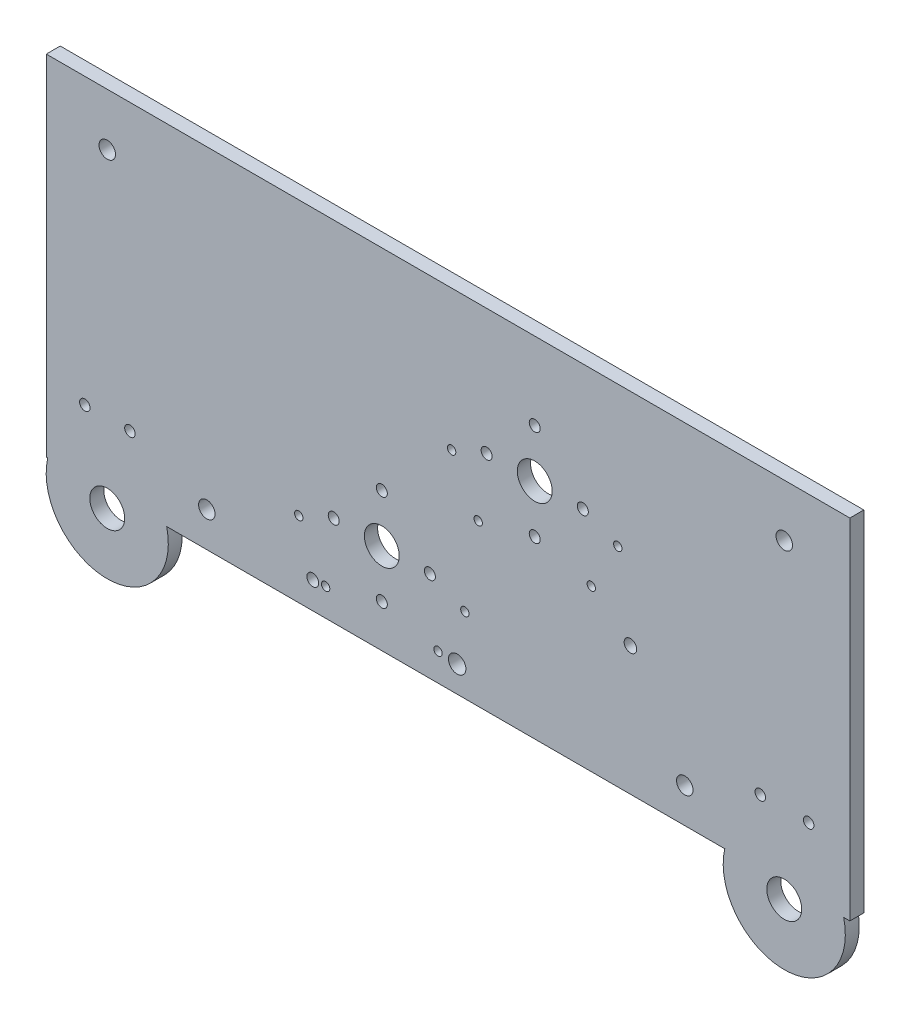
SolidWorks part; units mm, degrees
ref_plane "Front Plane" through (0, 0, 0) normal (0, 0, 1) x (1, 0, 0)
ref_plane "Top Plane" through (0, 0, 0) normal (0, 1, 0) x (1, 0, 0)
ref_plane "Right Plane" through (0, 0, 0) normal (1, 0, 0) x (0, 0, -1)
sketch "Sketch2" plane through (0, 0, 0) normal (0, 0, 1) x (1, 0, 0)
  line L1 (-143.383, -31.75) -> (143.383, -31.75)
  line L2 (-143.383, -31.75) -> (-143.383, 31.75)
  line L3 (-143.383, 31.75) -> (143.383, 31.75)
  line L4 (143.383, -31.75) -> (143.383, 31.75)
  line L5 (-143.383, -31.75) -> (143.383, 31.75) construction
  line L6 (-143.383, 31.75) -> (143.383, -31.75) construction
  line L16 (-143.383, 31.75) -> (143.383, 31.75)
  line L17 (-143.383, 31.75) -> (-143.383, 95.25)
  line L18 (-143.383, 95.25) -> (143.383, 95.25)
  line L19 (143.383, 31.75) -> (143.383, 95.25)
  circle A0 centre (-123.317, -36.83) radius 6.35
  circle A1 centre (123.063, -36.83) radius 6.35
  point P0 (0, 0)
  dimension "D3" = 20.066
  dimension "D5" = 5.08
  dimension "D7" = 63.5
  dimension "D1" = 63.5
  dimension "D2" = 286.766
  dimension "D6" = 20.32
extrude "Boss-Extrude1" add sketch "Sketch2" against normal blind 5.0749 contours A1 L1 L4 L3 L2 A0 | L3 L19 L18 L17 region at (0.0001, 0.0226, 0) region at (0, 63.5, 0)
ref_plane "Plane1" through (-143.383, 95.25, 0) normal (0, 1, 0) x (1, 0, 0)
ref_plane "Plane2" through (0, 0, -5.0749) normal (0, 0, -1) x (-1, 0, 0)
sketch "Sketch6" plane through (0, 0, -5.0749) normal (0, 0, -1) x (-1, 0, 0)
  line L0 (-116.713, -36.83) -> (-129.413, -36.83) construction
  line L1 (-123.063, -30.48) -> (-123.063, -43.18) construction
  line L3 (123.317, -30.48) -> (123.317, -43.18) construction
  line L4 (123.317, -43.18) -> (116.967, -36.83) construction
  line L6 (116.967, -36.83) -> (129.667, -36.83) construction
  circle A2 centre (-123.063, -36.83) radius 6.35 construction
  circle A3 centre (-123.063, -36.83) radius 22.225
  circle A4 centre (123.317, -36.83) radius 6.35 construction
  circle A5 centre (123.317, -36.83) radius 22.225
  dimension "D1" = 44.45
  dimension "D2" = 44.45
extrude "Boss-Extrude3" add sketch "Sketch6" against normal blind 5.0749
extrude "Cut-Extrude2" cut sketch "Sketch2<3>" against normal blind 5.588 contours A0 | A1
sketch "Sketch2<3>" plane through (0, 0, 0) normal (0, 0, 1) x (1, 0, 0) same geometry as "Sketch2"
sketch "Sketch8" plane through (0, 0, -5.0749) normal (0, 0, -1) x (-1, 0, 0)
  line L0 (145.5039, -31.75) -> (145.5039, 95.25) construction
  line L1 (198.383, 95.25) -> (88.383, 95.25) construction
  line L2 (143.383, -27.2746) -> (143.383, 95.25) construction
  line L3 (101.6804, -31.75) -> (170.7618, -31.75) construction
  line L4 (145.5039, 95.25) -> (142.7757, 95.25)
  line L5 (145.5039, 95.25) -> (145.5039, -31.75)
  line L6 (145.5039, -31.75) -> (142.7757, -31.75)
  line L7 (142.7757, 95.25) -> (142.7757, -31.75)
  dimension "D1" = 2.1209
extrude "Boss-Extrude4" add sketch "Sketch8" against normal blind 5.0749
sketch "Sketch9" plane through (0, 0, -5.0749) normal (0, 0, -1) x (-1, 0, 0)
  line L0 (-114.4501, -31.75) -> (-154.5549, -31.75) construction
  line L1 (-146.9463, 95.25) -> (-143.383, 95.25)
  line L2 (-146.9463, 95.25) -> (-146.9463, -31.75)
  line L3 (-146.9463, -31.75) -> (-143.383, -31.75)
  line L4 (-143.383, 95.25) -> (-143.383, -31.75)
  line L5 (-143.383, -27.8273) -> (-143.383, 95.25) construction
  line L6 (101.6804, -31.75) -> (-101.4264, -31.75) construction
  dimension "D1" = 3.5633
extrude "Boss-Extrude5" add sketch "Sketch9" against normal blind 5.0749
sketch "Sketch12" plane through (0, 0, 0) normal (0, 0, 1) x (1, 0, 0)
  line L0 (-123.317, -43.18) -> (-123.317, 95.25) construction
  line L1 (-145.5039, 95.25) -> (146.9463, 95.25) construction
  line L2 (-123.317, 95.25) -> (123.063, -43.18) construction
  line L3 (123.063, -43.18) -> (123.063, 95.25) construction
  line L4 (123.063, 95.25) -> (-123.317, -43.18) construction
  line L5 (-123.317, -43.18) -> (-123.317, 76.2) construction
  line L6 (-123.317, 76.2) -> (123.063, 76.2) construction
  circle A0 centre (-123.317, -36.83) radius 6.35 construction
  circle A1 centre (123.063, -36.83) radius 6.35 construction
  circle A2 centre (-123.317, 76.2) radius 3
  circle A3 centre (123.063, 76.2) radius 3
  dimension "D1" = 19.05
extrude "Cut-Extrude3" cut sketch "Sketch12" against normal blind 400.05
sketch "Sketch13" plane through (0, 0, -5.0749) normal (0, 0, -1) x (-1, 0, 0)
  line L0 (101.6804, -31.75) -> (-101.4264, -31.75) construction
  line L3 (-146.9463, 95.25) -> (-146.9463, -31.75) construction
  circle A0 centre (23.3906, 1.27) radius 22.86
  circle A1 centre (-32.258, 49.53) radius 22.86
  circle A4 centre (-32.258, 67.0306) radius 2
  circle A5 centre (-14.7574, 49.53) radius 2
  circle A6 centre (-32.258, 32.0294) radius 2
  circle A7 centre (-49.7586, 49.53) radius 2
  circle A8 centre (23.3906, 18.7706) radius 2
  circle A9 centre (40.8912, 1.27) radius 2
  circle A10 centre (23.3906, -16.2306) radius 2
  circle A11 centre (5.89, 1.27) radius 2
  circle A12 centre (-32.258, 49.53) radius 6.35
  circle A13 centre (23.3906, 1.27) radius 6.35
  dimension "D1" = 33.02
  dimension "D3" = 81.28
  dimension "D4" = 45.72
  dimension "D6" = 17.5006
  dimension "D2" = 114.6883
  dimension "D5" = 73.66
  dimension "D7" = 17.5006
  dimension "D8" = 17.5006
  dimension "D9" = 17.5006
  dimension "D10" = 17.5006
  dimension "D11" = 17.5006
  dimension "D12" = 17.5006
  dimension "D13" = 17.5006
ref_plane "Plane3" through (0, 0, -114.2949) normal (0, 0, -1) x (-1, 0, 0)
mirror "Mirror1" about plane through (0, 0, -114.2949) normal (0, 0, -1) of bodies 108 110
delete or keep bodies "Body-Delete/Keep 1" type delete bodies bodies 108
extrude "Cut-Extrude10" cut sketch "Sketch13<3>" along normal blind 1549.4 contours A8 | A11 | A9 | A10 | A4 | A5 | A6 | A7 region at (32.258, 67.0306, -5.0749) region at (14.7574, 49.53, -5.0749) region at (32.258, 32.0294, -5.0749) region at (49.7586, 49.53, -5.0749) region at (-23.3906, 18.7706, -5.0749) region at (-40.8912, 1.27, -5.0749) region at (-23.3906, -16.2306, -5.0749) region at (-5.89, 1.27, -5.0749)
sketch "Sketch13<3>" plane through (0, 0, -5.0749) normal (0, 0, -1) x (-1, 0, 0) same geometry as "Sketch13"
sketch "Sketch15" plane through (0, 0, -223.5149) normal (0, 0, 1) x (1, 0, 0)
  line L0 (-145.5039, -31.75) -> (-145.5039, 95.25) construction
  line L2 (-101.6804, -31.75) -> (101.4264, -31.75) construction
  line L3 (146.9463, 95.25) -> (146.9463, -31.75) construction
  circle A0 centre (-87.0839, -19.05) radius 2.9972
  circle A1 centre (86.868, -19.05) radius 2.9972
  dimension "D1" = 58.42
  dimension "D2" = 60.0783
  dimension "D3" = 12.7
  dimension "D4" = 12.7
extrude "Cut-Extrude11" cut sketch "Sketch15" against normal blind 1549.4
extrude "Cut-Extrude12" cut sketch "Sketch13<4>" along normal blind 1549.4 contours A13 | A12 region at (32.258, 49.53, -5.0749) region at (-23.3906, 1.27, -5.0749)
sketch "Sketch13<4>" plane through (0, 0, -5.0749) normal (0, 0, -1) x (-1, 0, 0) same geometry as "Sketch13"
extrude "Cut-Extrude13" cut sketch "Sketch13" along normal blind 1549.4 from offset 223.266
sketch "Sketch16" plane through (0, 0, -223.5149) normal (0, 0, 1) x (1, 0, 0)
  line L0 (32.258, 18.8185) -> (32.258, 26.7289) construction
  line L1 (32.258, 26.7289) -> (11.6837, 26.7289) construction
  line L2 (11.6837, 26.7289) -> (52.8323, 26.7289) construction
  line L3 (52.8323, 26.7289) -> (62.4869, 44.1073) construction
  line L4 (62.4869, 44.1073) -> (2.0074, 44.2293) construction
  line L5 (-23.3906, -29.464) -> (-23.3906, -21.6773) construction
  line L6 (-23.3906, -21.6773) -> (-2.9456, -21.6773) construction
  line L7 (-2.9456, -21.6773) -> (-43.8357, -21.6773) construction
  line L8 (-43.8357, -21.6773) -> (-53.6181, -4.2867) construction
  line L9 (-53.6181, -4.2867) -> (6.8369, -4.2867) construction
  line L10 (6.8369, -4.2867) -> (-2.9456, -21.6773) construction
  circle A0 centre (-23.3906, 1.27) radius 30.734
  circle A1 centre (32.258, 49.53) radius 30.7115
  circle A2 centre (2.0074, 44.2293) radius 1.524
  circle A3 centre (11.6837, 26.7289) radius 1.524
  circle A4 centre (52.8323, 26.7289) radius 1.524
  circle A5 centre (62.4869, 44.1073) radius 1.524
  circle A6 centre (-53.6181, -4.2867) radius 1.524
  circle A7 centre (-43.8357, -21.6773) radius 1.524
  circle A8 centre (-2.9456, -21.6773) radius 1.524
  circle A9 centre (6.8369, -4.2867) radius 1.524
extrude "Cut-Extrude14" cut sketch "Sketch16" against normal blind 6.35 and the other way blind 2.54 contours A0 A6 | A0 A6 | A0 A7 | A0 A7 | A0 A8 | A0 A8 | A0 A9 | A0 A9 | A1 A2 | A1 A2 | A1 A3 | A1 A3 | A1 A4 | A1 A5 | A1 A5 | A4 region at (-52.9753, -4.1686, -223.5149) region at (-54.2475, -4.4024, -223.5149) region at (7.4663, -4.4024, -223.5149) region at (6.1941, -4.1686, -223.5149) region at (-43.4009, -21.1893, -223.5149) region at (-44.2614, -22.1551, -223.5149) region at (-2.5199, -22.1551, -223.5149) region at (-3.3803, -21.1893, -223.5149) region at (2.6512, 44.3421, -223.5149) region at (1.3771, 44.1188, -223.5149) region at (63.1168, 43.9943, -223.5149) region at (61.8436, 44.2227, -223.5149) region at (12.1215, 27.2141, -223.5149) region at (11.2549, 26.2538, -223.5149) region at (52.3945, 27.2141, -223.5149)
sketch "Sketch17" plane through (0, 0, -223.5149) normal (0, 0, 1) x (1, 0, 0)
  line L0 (-123.317, -59.055) -> (-123.317, -35.5618) construction
  line L1 (-123.317, -35.5618) -> (-131.4747, -8.3312) construction
  line L2 (-131.4747, -8.3312) -> (-115.0599, -8.3312) construction
  line L3 (-115.0599, -8.3312) -> (-123.317, -35.5618) construction
  line L4 (123.063, -59.055) -> (123.063, -35.433) construction
  line L5 (123.063, -35.433) -> (114.3463, -8.2477) construction
  line L6 (114.3463, -8.2477) -> (131.955, -8.2477) construction
  line L7 (131.955, -8.2477) -> (123.063, -35.433) construction
  arc A0 (-144.9536, -31.75) -> (-101.6804, -31.75) centre (-123.317, -36.83) ccw construction
  circle A1 centre (-131.4747, -8.3312) radius 1.905
  circle A2 centre (-115.0599, -8.3312) radius 1.905
  circle A3 centre (-123.317, -35.5618) radius 1.905
  arc A4 (101.4264, -31.75) -> (144.6996, -31.75) centre (123.063, -36.83) ccw construction
  circle A5 centre (123.063, -35.433) radius 1.905
  circle A6 centre (114.3463, -8.2477) radius 1.905
  circle A7 centre (131.955, -8.2477) radius 1.905
extrude "Cut-Extrude15" cut sketch "Sketch17" against normal blind 6.35
sketch "Sketch18" plane through (0, 0, -223.5149) normal (0, 0, 1) x (1, 0, 0)
  line L0 (-145.5039, -22.8292) -> (-48.523, -22.8292) construction
  line L1 (-48.523, -22.8292) -> (-48.523, -31.75) construction
  line L2 (-101.6804, -31.75) -> (101.4264, -31.75) construction
  line L3 (-48.523, -31.75) -> (-48.523, -21.971) construction
  line L4 (-87.0839, -19.05) -> (86.868, -19.05) construction
  line L5 (86.868, -19.05) -> (4.0335, -19.05) construction
  line L6 (4.0335, -31.75) -> (4.0335, -22.225) construction
  line L7 (67.0809, -31.75) -> (67.0809, 15.0683) construction
  circle A0 centre (-48.523, -21.971) radius 2.159
  circle A1 centre (4.0335, -22.225) radius 3.175
  circle A2 centre (67.0809, 15.0683) radius 2.286
  dimension "D1" = 9.525
extrude "Cut-Extrude16" cut sketch "Sketch18" against normal blind 6.35
